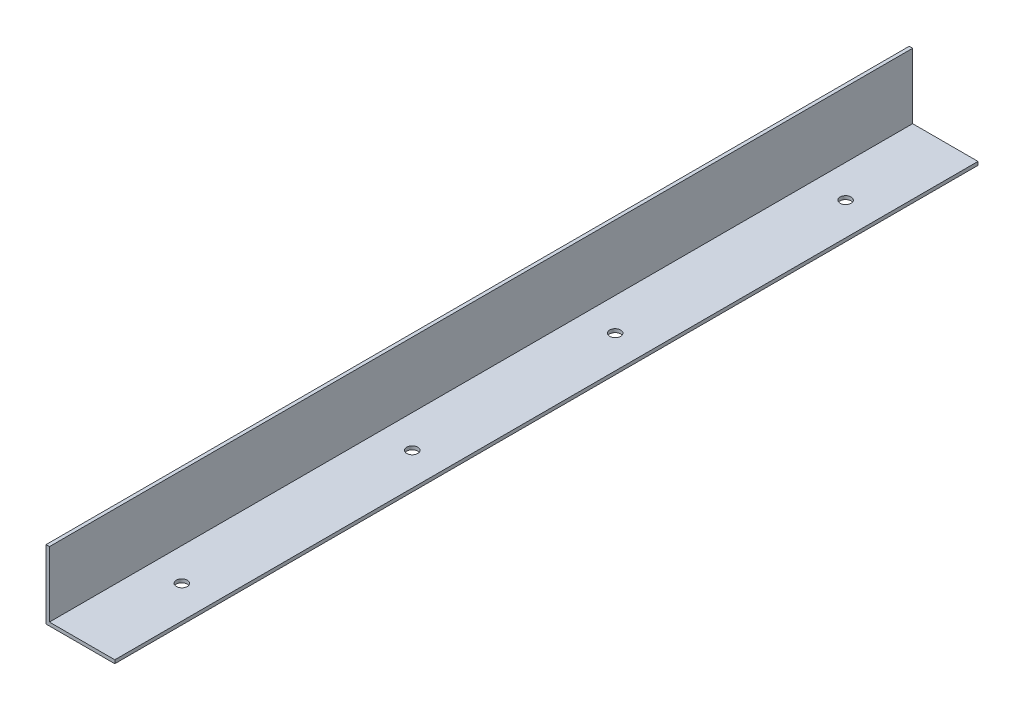
SolidWorks part; units mm, degrees
material "1060 Сплав"
ref_plane "Спереди" through (0, 0, 0) normal (0, 0, 1) x (1, 0, 0)
ref_plane "Сверху" through (0, 0, 0) normal (0, 1, 0) x (1, 0, 0)
ref_plane "Справа" through (0, 0, 0) normal (1, 0, 0) x (0, 0, -1)
sketch "Эскиз1" plane through (0, 0, 0) normal (0, 0, 1) x (1, 0, 0)
  line L0 (0, 0) -> (0, 20)
  line L1 (0, 20) -> (1, 20)
  line L2 (1, 20) -> (1, 1)
  line L3 (1, 1) -> (20, 1)
  line L4 (20, 1) -> (20, 0)
  line L5 (20, 0) -> (0, 0)
  dimension "D1" = 20
  dimension "D2" = 1
extrude "Бобышка-Вытянуть1" add sketch "Эскиз1" along normal blind 251
sketch "Эскиз2" plane through (0, 1, 0) normal (0, 1, 0) x (1, 0, 0)
  line L0 (10.5, 0) -> (10.5, -251) construction
  line L1 (20, 0) -> (1, 0) construction
  line L2 (20, -251) -> (1, -251) construction
  line L3 (20, -125.5) -> (10.5, -125.5) construction
  line L4 (20, -251) -> (20, 0) construction
  line L5 (10.5, -29) -> (10.5, -96) construction
  line L6 (20, -62.5) -> (10.5, -62.5) construction
  circle A0 centre (10.5, -29) radius 1.6
  circle A1 centre (10.5, -96) radius 1.6
  circle A2 centre (10.5, -222) radius 1.6
  circle A3 centre (10.5, -155) radius 1.6
  point P14 (20, -62.5)
  point P17 (10.5, -62.5)
  dimension "D1" = 3.2
  dimension "D2" = 3.2
  dimension "D3" = 67
  dimension "D4" = 125.5
  dimension "D5" = 63
extrude "Вырез-Вытянуть1" cut sketch "Эскиз2" against normal through all
